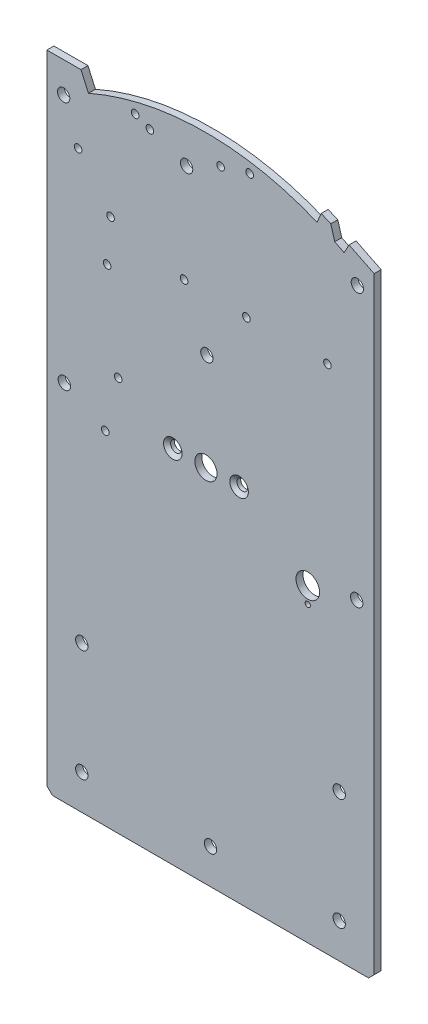
SolidWorks part; units mm, degrees
material "6061-T6 (SS)"
ref_plane "Front Plane" through (0, 0, 0) normal (0, 0, 1) x (1, 0, 0)
ref_plane "Top Plane" through (0, 0, 0) normal (0, 1, 0) x (1, 0, 0)
ref_plane "Right Plane" through (0, 0, 0) normal (1, 0, 0) x (0, 0, -1)
sketch "Sketch1" plane through (0, 0, 0) normal (0, 0, 1) x (1, 0, 0)
  line L0 (-37.0142, -65.193) -> (-37.0142, -242.993)
  line L1 (111.7057, -78.8372) -> (111.7057, -242.993)
  line L2 (111.7057, -242.993) -> (-37.0142, -242.993)
  line L3 (-28.4308, -65.1684) -> (-21.4969, -65.1485)
  line L4 (-21.4969, -65.1485) -> (-20.0556, -68.4088)
  line L41 (111.7057, -78.8372) -> (100.3159, -73.2191)
  line L42 (100.3159, -73.2191) -> (98.0489, -77.4075)
  line L43 (93.8204, -75.2164) -> (91.992, -69.0732)
  line L44 (91.992, -69.0732) -> (87.6255, -67.1718)
  line L45 (87.6255, -67.1718) -> (85.8005, -71.5708)
  line L46 (-18.13, -72.7646) -> (-20.0556, -68.4088)
  line L47 (-25.8634, -70.9762) -> (-28.4308, -65.1684) construction
  line L48 (-28.4308, -65.1684) -> (-37.0142, -65.193)
  line L75 (-20.0556, -68.4088) -> (-25.8634, -70.9762) construction
  arc A5 (98.0489, -77.4075) -> (93.8204, -75.2164) centre (35.2286, -193.468) ccw
  arc A9 (85.8005, -71.5708) -> (-18.13, -72.7646) centre (35.2286, -193.468) ccw
  dimension "D2" = 177.8
  dimension "D1" = 148.72
extrude "Boss-Extrude1" add sketch "Sketch1" against normal blind 3.175
sketch "Sketch2" plane through (0, 0, 0) normal (0, 0, 1) x (1, 0, 0)
  line L0 (111.7057, -231.472) -> (111.7057, -78.8372) construction
  line L1 (-21.4969, -65.1485) -> (-37.0142, -65.193) construction
  circle A0 centre (35.2684, -193.372) radius 5.0419
  dimension "D1" = 10.0838
  dimension "D2" = 76.4373
  dimension "D3" = 128.3861
extrude "Cut-Extrude1" cut sketch "Sketch2" against normal through all
hole_wizard "#4 Clearance Hole1" positions "Sketch4" profile "Sketch3" hole size "#4" standard "ANSI Inch" end condition through all
sketch "Sketch4" plane through (0, 0, 0) normal (0, 0, 1) x (1, 0, 0)
  point P0 (41.9398, -71.4888)
  point P3 (9.7895, -73.0113)
  point P6 (90.4886, -124.9671)
  point P9 (53.6587, -125.0729)
  point P12 (25.3388, -124.3417)
  point P15 (-9.6344, -135.8882)
  point P19 (55.1452, -67.7003)
  point P23 (3.102, -70.2707)
sketch "Sketch3" plane through (41.9398, -71.4888, 0) normal (1, 0, 0) x (0, -1, 0)
  line L0 (0, 0) -> (0, 3.175)
  line L1 (0, 3.175) -> (1.7272, 3.175)
  line L2 (1.7272, 3.175) -> (1.7272, 0)
  line L5 (1.7272, 0) -> (0, 0)
  line L11 (0, -6.35) -> (0, 107.95) construction
  dimension "Thru Hole Dia." = 3.4544
  dimension "Thru Hole Depth" = 3.175
hole_wizard "#10 Clearance Hole1" positions "Sketch6" profile "Sketch5" hole size "#10" standard "ANSI Inch" end condition through all
sketch "Sketch6" plane through (0, 0, 0) normal (0, 0, 1) x (1, 0, 0)
  point P0 (-29.3942, -79.072)
  point P3 (104.0857, -87.327)
  point P9 (35.696, -148.922)
  point P12 (26.4858, -79.072)
sketch "Sketch5" plane through (-29.3942, -79.072, 0) normal (1, 0, 0) x (0, -1, 0)
  line L0 (0, 0) -> (0, 3.175)
  line L1 (0, 3.175) -> (2.8067, 3.175)
  line L2 (2.8067, 3.175) -> (2.8067, 0)
  line L5 (2.8067, 0) -> (0, 0)
  line L11 (0, -6.35) -> (0, 107.95) construction
  dimension "Thru Hole Dia." = 5.6134
  dimension "Thru Hole Depth" = 3.175
hole_wizard "#4 Clearance Hole2" positions "Sketch8" profile "Sketch7" hole size "#4" standard "ANSI Inch" end condition through all
sketch "Sketch8" plane through (0, 0, 0) normal (0, 0, 1) x (1, 0, 0)
  point P0 (-8.0737, -116.3194)
  point P3 (-22.8122, -96.7821)
  point P12 (-10.4786, -201.738)
  point P15 (-4.604, -177.9805)
sketch "Sketch7" plane through (-8.0737, -116.3194, 0) normal (1, 0, 0) x (0, -1, 0)
  line L0 (0, 0) -> (0, 3.175)
  line L1 (0, 3.175) -> (1.7272, 3.175)
  line L2 (1.7272, 3.175) -> (1.7272, 0)
  line L5 (1.7272, 0) -> (0, 0)
  line L11 (0, -6.35) -> (0, 107.95) construction
  dimension "Thru Hole Dia." = 3.4544
  dimension "Thru Hole Depth" = 3.175
hole_wizard "27/64 (0.42188) Diameter Hole1" positions "Sketch10" profile "Sketch9" hole size "27/64" standard "ANSI Inch" end condition through all
sketch "Sketch10" plane through (0, 0, 0) normal (0, 0, 1) x (1, 0, 0)
  point P0 (81.5512, -216.6701)
sketch "Sketch9" plane through (81.5512, -216.6701, 0) normal (1, 0, 0) x (0, -1, 0)
  line L0 (0, 0) -> (0, 3.175)
  line L1 (0, 3.175) -> (5.3579, 3.175)
  line L2 (5.3579, 3.175) -> (5.3579, 0)
  line L5 (5.3579, 0) -> (0, 0)
  line L11 (0, -6.35) -> (0, 107.95) construction
  dimension "Thru Hole Dia." = 10.7158
  dimension "Thru Hole Depth" = 3.175
hole_wizard "3/32 (0.09375) Diameter Hole1" positions "Sketch12" profile "Sketch11" hole size "3/32" standard "ANSI Inch" end condition through all
sketch "Sketch12" plane through (0, 0, 0) normal (0, 0, 1) x (1, 0, 0)
  circle A0 centre (81.5512, -216.6701) radius 5.3579 construction
  point P0 (81.5512, -224.0361)
  dimension "D1" = 7.366
sketch "Sketch11" plane through (81.5512, -224.0361, 0) normal (1, 0, 0) x (0, -1, 0)
  line L0 (0, 0) -> (0, 3.175)
  line L1 (0, 3.175) -> (1.1906, 3.175)
  line L2 (1.1906, 3.175) -> (1.1906, 0)
  line L5 (1.1906, 0) -> (0, 0)
  line L11 (0, -6.35) -> (0, 107.95) construction
  dimension "Thru Hole Dia." = 2.3812
  dimension "Thru Hole Depth" = 3.175
hole_wizard "#10 Clearance Hole2" positions "Sketch14" profile "Sketch13" hole size "#10" standard "ANSI Inch" end condition through all
sketch "Sketch14" plane through (0, 0, 0) normal (0, 0, 1) x (1, 0, 0)
  circle A0 centre (-29.0767, -192.193) radius 2.8067 construction
  circle A1 centre (103.7682, -211.243) radius 2.8067 construction
  point P0 (-29.0767, -192.193)
  point P6 (103.7682, -211.243)
sketch "Sketch13" plane through (-29.0767, -192.193, 0) normal (1, 0, 0) x (0, -1, 0)
  line L0 (0, 0) -> (0, 3.175)
  line L1 (0, 3.175) -> (2.8067, 3.175)
  line L2 (2.8067, 3.175) -> (2.8067, 0)
  line L5 (2.8067, 0) -> (0, 0)
  line L11 (0, -6.35) -> (0, 107.95) construction
  dimension "Thru Hole Dia." = 5.6134
  dimension "Thru Hole Depth" = 3.175
sketch "Sketch15" plane through (0, 0, 0) normal (0, 0, 1) x (1, 0, 0)
  line L0 (109.1657, -357.293) -> (-34.4742, -357.293) construction
  line L1 (-37.0142, -242.993) -> (111.7057, -242.993)
  line L2 (-37.0142, -242.993) -> (-37.0142, -357.293)
  line L3 (-37.0142, -357.293) -> (111.7057, -357.293)
  line L4 (111.7057, -242.993) -> (111.7057, -357.293)
extrude "Boss-Extrude2" add sketch "Sketch15" against normal through all
chamfer "Chamfer1" distance 2.54 angle 45 2 edges at (-37.0142, -357.293, -1.5875) (111.7057, -357.293, -1.5875)
hole_wizard "#10 Clearance Hole3" positions "Sketch16" profile "Sketch17" hole size "#10" standard "ANSI Inch" end condition through all
sketch "Sketch16" plane through (0, 0, 0) normal (0, 0, 1) x (1, 0, 0)
  point P0 (95.8307, -341.418)
  point P3 (37.3457, -341.418)
  point P6 (-21.1392, -341.418)
  point P9 (95.8307, -290.618)
  point P12 (-21.1392, -290.618)
sketch "Sketch17" plane through (95.8307, -341.418, 0) normal (1, 0, 0) x (0, -1, 0)
  line L0 (0, 0) -> (0, 3.175)
  line L1 (0, 3.175) -> (2.8067, 3.175)
  line L2 (2.8067, 3.175) -> (2.8067, 0)
  line L5 (2.8067, 0) -> (0, 0)
  line L11 (0, -6.35) -> (0, 107.95) construction
  dimension "Thru Hole Dia." = 5.6134
  dimension "Thru Hole Depth" = 3.175
hole_wizard "CSK for #8 Flat Head Machine Screw (100)2" positions "Sketch18" profile "Sketch19" countersink size "#8" standard "ANSI Inch" end condition through all
sketch "Sketch18" plane through (0, 0, 0) normal (0, 0, 1) x (1, 0, 0)
  circle A0 centre (20.203, -193.372) radius 4.2164 construction
  circle A1 centre (50.3338, -193.372) radius 4.2164 construction
  point P0 (20.203, -193.372)
  point P2 (50.3338, -193.372)
sketch "Sketch19" plane through (20.203, -193.372, 0) normal (1, 0, 0) x (0, -1, 0)
  line L0 (0, 0) -> (0, 3.175)
  line L1 (0, 3.175) -> (2.4574, 3.175)
  line L2 (2.4574, 3.175) -> (2.4574, 1.4759)
  line L3 (2.4574, 1.4759) -> (4.2164, 0)
  line L5 (4.2164, 0) -> (0, 0)
  line L6 (-2.4574, 1.4759) -> (-4.2164, 0) construction
  line L11 (0, -6.35) -> (0, 107.95) construction
  dimension "Thru Hole Dia." = 4.9149
  dimension "Thru Hole Depth" = 3.175
  dimension "Near C'Sink Dia." = 8.4328
  dimension "Near C'Sink Angle" = 100
